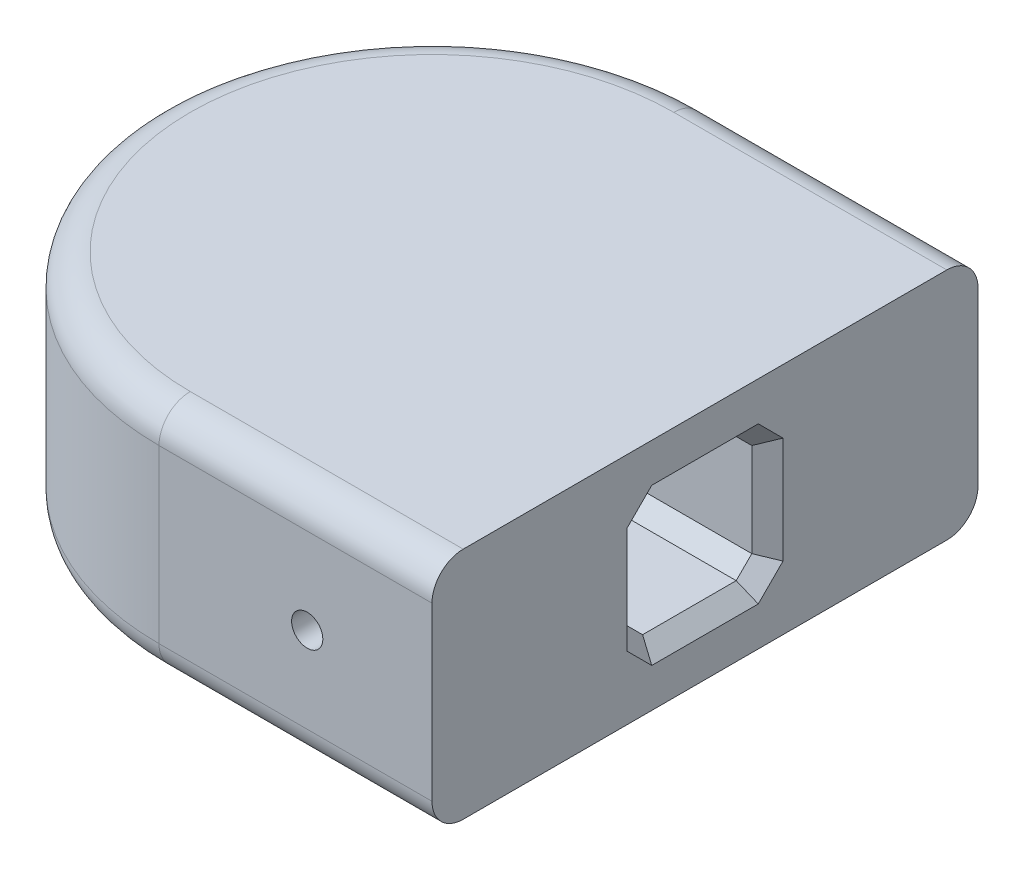
SolidWorks part; units mm, degrees
ref_plane "Front Plane" through (0, 0, 0) normal (0, 0, 1) x (1, 0, 0)
ref_plane "Top Plane" through (0, 0, 0) normal (0, 1, 0) x (1, 0, 0)
ref_plane "Right Plane" through (0, 0, 0) normal (1, 0, 0) x (0, 0, -1)
sketch "Sketch1" plane through (0, 0, 0) normal (0, 1, 0) x (1, 0, 0)
  line L1 (0, 0) -> (44.45, 0)
  line L2 (0, 0) -> (0, 44.45)
  line L3 (0, 44.45) -> (44.45, 44.45)
  line L4 (44.45, 0) -> (44.45, 44.45)
  line L5 (22.225, 44.45) -> (22.225, 0)
  arc A0 (22.225, 44.45) -> (22.225, 0) centre (22.225, 22.225) ccw
  dimension "D1" = 44.45
  dimension "D2" = 44.45
extrude "Main body extrude" add sketch "Sketch1" along normal blind 19.05 contours L5 A0 | L3 L5 L1 L4 region at (33.3375, 0, -22.225) region at (12.7924, 0, -22.225)
sketch "Sketch2" plane through (44.45, 0, 0) normal (1, 0, 0) x (0, 0, -1)
  line L0 (22.225, 19.05) -> (22.225, 0) construction
  line L1 (0, 19.05) -> (44.45, 19.05) construction
  line L2 (0, 0) -> (44.45, 0) construction
  line L3 (44.45, 9.525) -> (22.225, 9.525) construction
  line L4 (44.45, 19.05) -> (44.45, 0) construction
  line L6 (17.145, 14.605) -> (27.305, 14.605)
  line L7 (17.145, 14.605) -> (17.145, 4.445)
  line L8 (17.145, 4.445) -> (27.305, 4.445)
  line L9 (27.305, 14.605) -> (27.305, 4.445)
  line L10 (17.145, 14.605) -> (27.305, 4.445) construction
  line L11 (17.145, 4.445) -> (27.305, 14.605) construction
  dimension "D1" = 10.16
  dimension "D2" = 10.16
extrude "Upper foot connection cut" cut sketch "Sketch2" against normal blind 15.24
sketch "Sketch3" plane through (0, 0, 0) normal (0, 0, 1) x (1, 0, 0)
  line L0 (44.45, 9.525) -> (29.21, 9.525) construction
  line L1 (44.45, 19.05) -> (44.45, 0) construction
  line L2 (29.21, 9.525) -> (34.29, 9.525)
  circle A0 centre (34.29, 9.525) radius 1.27
  dimension "D3" = 2.54
  dimension "D1" = 15.24
  dimension "D2" = 5.08
fillet "Fillet1" radius 2.54 6 edges at (0, 0, -22.225) (0, 19.05, -22.225) (33.3375, 19.05, -44.45) (33.3375, 0, -44.45) (33.3375, 0, 0) (33.3375, 19.05, 0)
extrude "Pinhole cut" cut sketch "Sketch3" against normal blind 64.516 contours A0
chamfer "Chamfer2" distance 1.27 angle 45 4 edges at (36.83, 14.605, -17.145) (36.83, 4.445, -17.145) (36.83, 14.605, -27.305) (36.83, 4.445, -27.305)
chamfer "Chamfer1" distance 1.27 angle 45 8 edges at (44.45, 14.605, -22.225) (44.45, 9.525, -27.305) (44.45, 4.445, -22.225) (44.45, 9.525, -17.145) (44.45, 13.97, -26.67) (44.45, 5.08, -26.67) (44.45, 5.08, -17.78) (44.45, 13.97, -17.78)
equation "\"heelLength\"=1.75"
equation "\"D1@Sketch1\"=\"heelLength\""
equation "\"heelWidth\"=1.75"
equation "\"D2@Sketch1\"=\"heelWidth\""
equation "\"heelHeight\"=0.75"
equation "\"D1@Main body extrude\" = \"heelHeight\""
